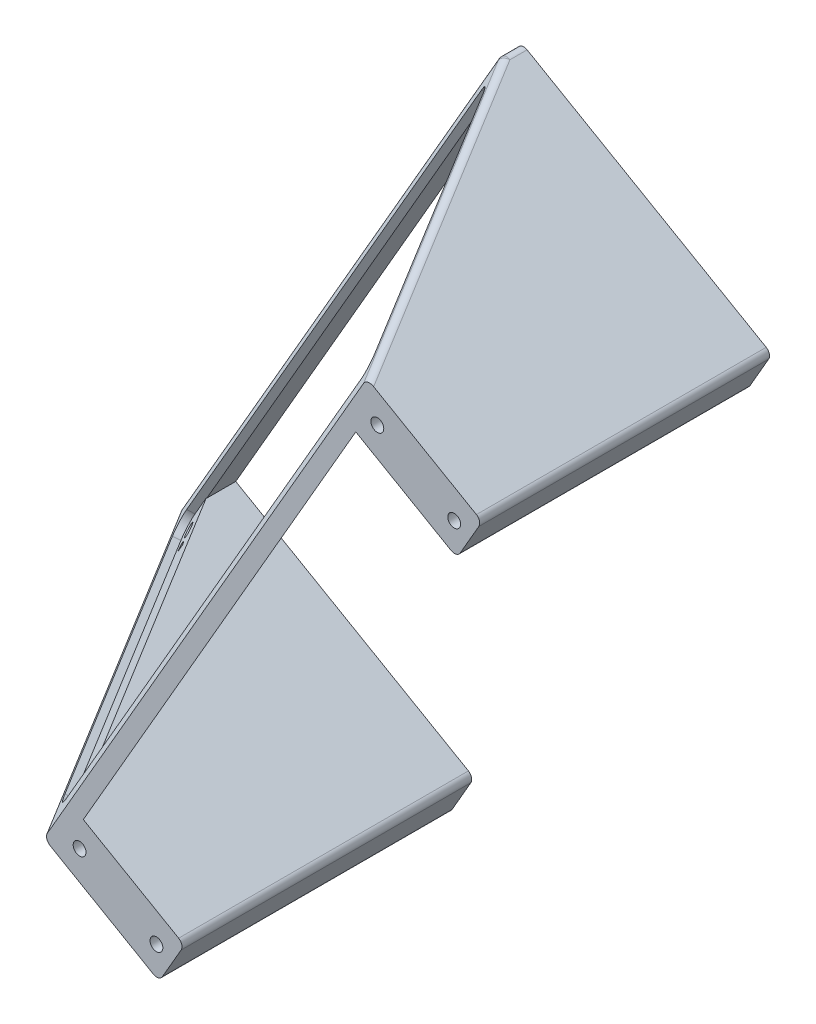
SolidWorks part; units mm, degrees
ref_plane "Front Plane" through (0, 0, 0) normal (0, 0, 1) x (1, 0, 0)
ref_plane "Top Plane" through (0, 0, 0) normal (0, 1, 0) x (1, 0, 0)
ref_plane "Right Plane" through (0, 0, 0) normal (1, 0, 0) x (0, 0, -1)
sketch "Sketch2" plane through (0, 0, 0) normal (0, 0, 1) x (1, 0, 0)
  line L1 (-105.8247, 132.2217) -> (-100.1097, 142.1204)
  line L3 (-100.1097, 142.1204) -> (-43.4673, 109.4179)
  line L4 (-105.8247, 132.2217) -> (-49.1823, 99.5192)
  line L5 (-100.1097, 142.1204) -> (-75.9594, 128.1772) construction
  line L6 (-105.8247, 132.2217) -> (-81.6744, 118.2785) construction
  line L7 (-43.4673, 109.4179) -> (-49.1823, 99.5192)
  line L10 (-97.5296, 136.9646) -> (-73.2229, 122.9311) construction
  dimension "D2" = 3.175
  dimension "D3" = 65.405
  dimension "D1" = 11.43
extrude "Boss-Extrude1" add sketch "Sketch2" along normal up to surface (65.5 mm away)
sketch "Sketch4" plane through (-102.9276, 59.4253, 68.6184) normal (0.75, -0.433, -0.5) x (-0.433, 0.25, -0.866)
  line L12 (12.0556, -70.1) -> (68.1896, -70.1)
  line L13 (8.6306, 66.675) -> (8.6306, -66.675)
  line L14 (68.1896, 70.1) -> (12.0556, 70.1)
  line L15 (71.6146, -66.675) -> (71.6146, 66.675)
  arc A12 (8.6306, -66.675) -> (12.0556, -70.1) centre (12.0556, -66.675) ccw
  arc A13 (12.0556, 70.1) -> (8.6306, 66.675) centre (12.0556, 66.675) ccw
  arc A14 (71.6146, 66.675) -> (68.1896, 70.1) centre (68.1896, 66.675) ccw
  arc A15 (68.1896, -70.1) -> (71.6146, -66.675) centre (68.1896, -66.675) ccw
extrude "Cut-Extrude1" cut sketch "Sketch4" against normal through all
sketch "Sketch5" plane through (-104.0706, 60.0852, 69.3804) normal (-0.75, 0.433, 0.5) x (0.433, -0.25, 0.866)
  line L1 (95.9817, 114.9073) -> (-190.8343, 114.9073)
  line L2 (95.9817, 114.9073) -> (95.9817, -159.5985)
  line L3 (95.9817, -159.5985) -> (-190.8343, -159.5985)
  line L4 (-190.8343, 114.9073) -> (-190.8343, -159.5985)
extrude "Cut-Extrude2" cut sketch "Sketch5" along normal through all
fillet "Fillet1" radius 1.5 4 edges at (-49.1823, 99.5192, 32.75) (-76.1118, 115.067, 63.7031) (-43.4673, 109.4179, 32.75) (-84.804, 133.2836, 34.8887)
sketch "Sketch6" plane through (-102.9276, 59.4253, 68.6184) normal (-0.75, 0.433, 0.5) x (0.433, -0.25, 0.866)
  circle A0 centre (-12.4366, 66.2953) radius 1.45
  circle A1 centre (-67.8086, 66.2953) radius 1.45
  dimension "D1" = 2.9
extrude "Cut-Extrude3" cut sketch "Sketch6" against normal blind 12.7
fillet "Fillet2" radius 1.5 1 edges at (-100.1097, 142.1204, 0.6387) tangent propagation no
ref_plane "Plane1" through (0, 0, 0) normal (0.5, 0.866, 0) x (0.866, -0.5, 0)
mirror "Mirror2" about plane through (0, 0, 0) normal (0.5, 0.866, 0) of bodies 104
sketch "Sketch8" plane through (30.7975, 53.3428, 0) normal (-0.5, -0.866, 0) x (0.866, -0.5, 0)
  line L2 (-154.5827, 6.555) -> (-155.9777, 7.3604)
  line L3 (-155.9777, 7.3604) -> (-157.7577, 4.2773) construction
  line L4 (-154.6579, 6.5984) -> (-155.9777, 7.3604) construction
  line L5 (-154.5827, 6.555) -> (-154.5827, 0)
  line L6 (-157.7577, 0) -> (-93.8527, 0) construction
  line L7 (-154.5827, 0) -> (-157.7577, 0)
  line L8 (-123.1867, 61.1561) -> (-121.7361, 60.3186)
  line L9 (-121.7361, 60.3186) -> (-118.7446, 65.5)
  line L10 (-118.7446, 65.5) -> (-120.6788, 65.5)
  line L11 (-157.7577, 4.2773) -> (-157.7577, 0) construction
  line L12 (-120.6788, 65.5) -> (-122.4108, 65.5)
  line L13 (-122.4108, 65.5) -> (-124.4857, 61.9061)
  line L15 (-123.1867, 61.1561) -> (-120.6788, 65.5)
  line L16 (-120.6788, 65.5) -> (-122.4108, 65.5)
  line L17 (-122.4108, 65.5) -> (-124.4857, 61.9061)
  line L19 (-123.1867, 61.1561) -> (-120.6788, 65.5) construction
  line L20 (-155.9777, 7.3604) -> (-157.7577, 4.2773)
  line L21 (-157.7577, 4.2773) -> (-157.7577, 0)
  spline S1 degree 1 poles (-2722.5413, 1561.8942) (2474.8478, -1438.8197) knots -1999.984115 -1999.984115 2000.967839 2000.967839 only from (-124.4857, 61.9061) to (-123.1867, 61.1561)
  spline S2 degree 1 poles (-124.4857, 61.9061) (-123.1867, 61.1561) knots 0 0 1 1
  dimension "D1" = 3.175
  dimension "D3" = 3.175
  dimension "D2" = 0
extrude "Boss-Extrude2" add sketch "Sketch8" along normal blind 129.032 and the other way blind 6.35
fillet "Fillet3" radius 1.5 3 edges at (-172.5345, 15.7982, 4.1596) (-99.9489, 141.5202, 4.1596) (-136.6222, 78.8789, 4.2773)
sketch "Sketch9" plane through (0, 0, 65.5) normal (0, 0, 1) x (1, 0, 0)
  circle A0 centre (-67.1597, 116.4976) radius 1.45
  circle A1 centre (-49.7889, 106.4685) radius 1.45
  circle A2 centre (-134.4697, -0.0868) radius 1.45
  circle A3 centre (-117.0989, -10.1158) radius 1.45
extrude "Cut-Extrude4" cut sketch "Sketch9" against normal blind 12.7
sketch "Sketch12" plane through (0, 0, 0) normal (0, 0, -1) x (-1, 0, 0)
  circle A0 centre (163.8426, 16.8717) radius 1.45
  circle A1 centre (117.0989, -10.1158) radius 1.45
  circle A2 centre (96.5326, 133.456) radius 1.45
  circle A3 centre (49.7889, 106.4685) radius 1.45
  dimension "D1" = 2.9
extrude "Cut-Extrude5" cut sketch "Sketch12" against normal blind 12.7
